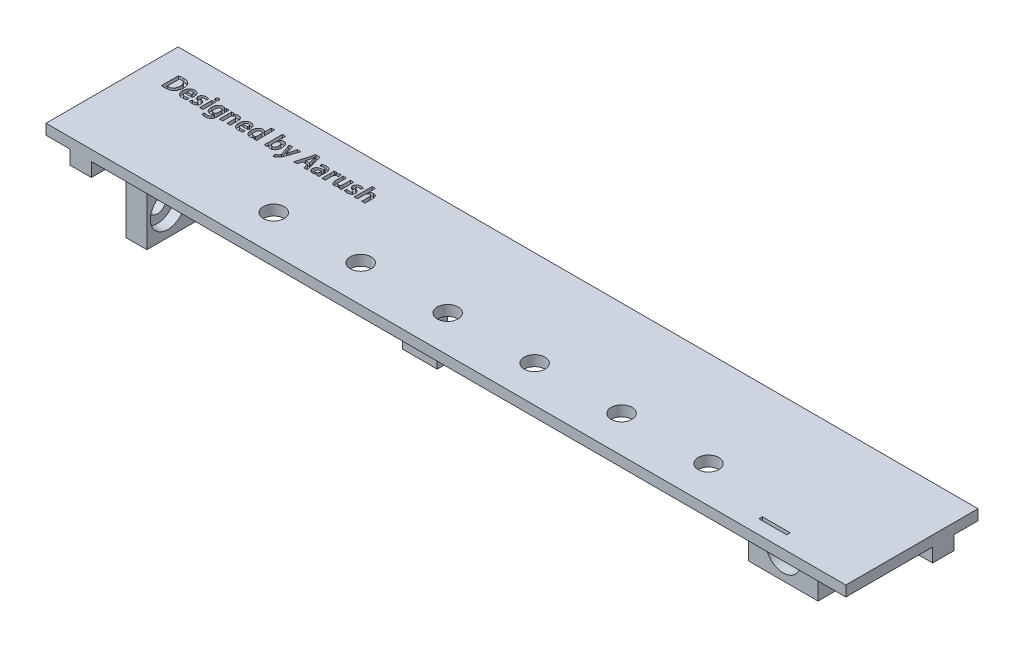
SolidWorks part; units mm, degrees
ref_plane "前视基准面" through (0, 0, 0) normal (0, 0, 1) x (1, 0, 0)
ref_plane "上视基准面" through (0, 0, 0) normal (0, 1, 0) x (1, 0, 0)
ref_plane "右视基准面" through (0, 0, 0) normal (1, 0, 0) x (0, 0, -1)
other "Configuration Table"
sketch "草图18" plane through (0, 0, 0) normal (0, 1, 0) x (1, 0, 0)
  line L1 (0, 0) -> (230, 0)
  line L2 (0, 0) -> (0, 36)
  line L3 (0, 36) -> (230, 36)
  line L4 (230, 0) -> (230, 36)
extrude "凸台-拉伸5" add sketch "草图18" along normal blind 3
sketch "草图20" plane through (0, 3, 0) normal (0, 1, 0) x (1, 0, 0)
  line L0 (0, 36) -> (0, 16)
  line L1 (0, 36) -> (0, 0) construction
  line L2 (0, 16) -> (18.0374, 16)
  line L3 (18.0374, 16) -> (18.0374, 1)
  line L4 (18.0374, 1) -> (0, 1)
  line L5 (0, 1) -> (0, 0)
  line L7 (0, 0) -> (230, 0)
  line L8 (0, 0) -> (0, -2)
  line L9 (0, -2) -> (230, -2)
  line L10 (230, 0) -> (230, -2)
  line M10 (0, 0) -> (230, 0)
extrude "凸台-拉伸6" add sketch "草图20" against normal blind 3 contours L10 L8 L9 M10 region at (115, 3, 1)
sketch "草图21" plane through (0, 3, 0) normal (0, 1, 0) x (1, 0, 0)
  line L0 (20, 16) -> (20, -2)
  line L1 (0, 36) -> (20, 36)
  line L2 (0, 36) -> (0, 16)
  line L3 (0, 16) -> (20, 16)
  line L4 (20, 36) -> (20, 16)
  line L5 (0, -2) -> (230, -2) construction
  line L6 (20, 16) -> (230, 16)
  line L8 (230, -2) -> (230, 36) construction
  line L10 (20, 16) -> (26, 16)
  line L11 (20, 16) -> (20, -2)
  line L12 (20, -2) -> (26, -2)
  line L13 (26, 16) -> (26, -2)
  line M10 (0, -2) -> (230, -2)
extrude "凸台-拉伸7" add sketch "草图21" against normal blind 23 contours L13 L6 L0 M10 region at (23, 3, -7)
sketch "草图23" plane through (0, 0, 0) normal (0, -1, 0) x (1, 0, 0)
  line L2 (230, -36) -> (0, -36) construction
  line L4 (6.95, -17) -> (6.95, -36)
  line L6 (6.95, -36) -> (10, -36)
  line L7 (13.05, -17) -> (13.05, 2)
  line L8 (6.95, -17) -> (6.95, 2)
  line L9 (6.95, 2) -> (13.05, 2)
  line L10 (13.05, -17) -> (13.05, -36)
  line L11 (13.05, -36) -> (10, -36)
extrude "凸台-拉伸8" add sketch "草图23" along normal blind 4 contours L4 L6 L11 L10 L7 L9 L8
sketch "草图24" plane through (0, 0, 0) normal (0, -1, 0) x (1, 0, 0)
  line L3 (20, -26) -> (20, -29.05)
  line L4 (20, -26) -> (20, -22.95)
  line L5 (20, -22.95) -> (230, -22.95)
  line L6 (20, -29.05) -> (230, -29.05)
  line L7 (230, -29.05) -> (230, -22.95)
extrude "凸台-拉伸9" add sketch "草图24" along normal blind 4 contours L3 L6 L7 L5 L4
sketch "草图25" plane through (26, 0, 0) normal (1, 0, 0) x (0, 0, -1)
  line L0 (-2, 0) -> (16, -20)
  circle A0 centre (7, -10) radius 2.6
extrude "切除-拉伸12" cut sketch "草图25" against normal blind 6 contours L0 A0 | L0 A0 region at (26, -9.2618, -7.8202) region at (26, -10.7382, -6.1798)
sketch "草图26" plane through (26, 0, 0) normal (1, 0, 0) x (0, 0, -1)
  circle A0 centre (7, -10) radius 5
extrude "切除-拉伸13" cut sketch "草图26" against normal blind 3
sketch "草图29" plane through (0, 0, 0) normal (0, -1, 0) x (1, 0, 0)
  line L12 (209, -2) -> (201, -2)
  line L13 (209, -2) -> (209, -3)
  line L14 (209, -3) -> (201, -3)
  line L15 (201, -2) -> (201, -3)
  circle A0 centre (55, -8.5) radius 3
  circle A7 centre (80, -8.5) radius 3
  circle A8 centre (105, -8.5) radius 3
  circle A9 centre (130, -8.5) radius 3
  circle A10 centre (155, -8.5) radius 3
  circle A11 centre (180, -8.5) radius 3
  circle A13 centre (205, -8.5) radius 3 [skipped]
  dimension "D1" = 7
extrude "切除-拉伸14" cut sketch "草图29" against normal blind 17
sketch "草图30" plane through (0, 0, 0) normal (0, -1, 0) x (1, 0, 0)
  line L8 (230, 2) -> (230, -22.95) construction
  line L9 (230, -16) -> (190, -16)
  line L11 (190, -16) -> (210, -16)
  line L12 (190, -16) -> (190, -13)
  line L13 (190, -13) -> (210, -13)
  line L14 (210, -16) -> (210, -13)
extrude "凸台-拉伸11" add sketch "草图30" along normal blind 20 contours L9 L14 L13 L12 region at (200, 0, -14.5)
sketch "草图31" plane through (0, 0, -13) normal (0, 0, 1) x (1, 0, 0)
  line L0 (190, 0) -> (210, -20)
  circle A0 centre (200, -10) radius 2.6
extrude "切除-拉伸15" cut sketch "草图31" against normal blind 20 contours L0 A0 | L0 A0 region at (200.7803, -9.2197, -13) region at (199.2197, -10.7803, -13)
sketch "草图32" plane through (0, 0, -13) normal (0, 0, 1) x (1, 0, 0)
  line L0 (210, -20) -> (210, 0) construction
  line L1 (190, -20) -> (210, -20)
  line L2 (190, -20) -> (190, -17)
  line L3 (190, -17) -> (210, -17)
  line L4 (210, -20) -> (210, -17)
extrude "切除-拉伸16" cut sketch "草图32" against normal blind 20
sketch "草图34" plane through (0, 0, -13) normal (0, 0, 1) x (1, 0, 0)
  line L1 (190, 0) -> (210, 0)
  line L2 (190, 0) -> (190, -17)
  line L3 (190, -17) -> (210, -17)
  line L4 (210, 0) -> (210, -17)
  circle A0 centre (200, -10) radius 5
extrude "凸台-拉伸12" add sketch "草图34" along normal blind 3 contours L2 L1 L4 L3 | A0
sketch "草图35" plane through (26, 0, 0) normal (1, 0, 0) x (0, 0, -1)
  line L0 (-2, 0) -> (16, 0) construction
  line L1 (-2, -20) -> (16, -20)
  line L2 (-2, -20) -> (-2, -17)
  line L3 (-2, -17) -> (16, -17)
  line L4 (16, -20) -> (16, -17)
  line L5 (-2, -17) -> (1, -17)
  line L6 (-2, -17) -> (-2, 0)
  line L7 (-2, 0) -> (1, 0)
  line L8 (1, -17) -> (1, 0)
  line M6 (16, 0) -> (-2, 0)
  line M7 (-2, 0) -> (-2, -20)
  line M8 (-2, -20) -> (16, -20)
  line M9 (16, -20) -> (16, 0)
extrude "切除-拉伸17" cut sketch "草图35" against normal blind 6 contours L3 L8 M6 M7 | L3 M7 M8 M9 region at (26, -18.5, -7) region at (26, -8.5, 0.5)
sketch "草图36" plane through (0, 0, 0) normal (0, -1, 0) x (1, 0, 0)
  line L0 (80, -8.5) -> (105, -8.5)
  line L1 (92.5, -16) -> (97.5, -16)
  line L2 (92.5, -16) -> (92.5, -8.5)
  line L3 (92.5, -16) -> (87.5, -16)
  line L5 (87.5, -16) -> (97.5, -16)
  line L6 (87.5, -16) -> (87.5, -13)
  line L7 (87.5, -13) -> (97.5, -13)
  line L8 (97.5, -16) -> (97.5, -13)
extrude "凸台-拉伸13" add sketch "草图36" along normal blind 17 contours L1 L8 L7 L2 | L7 L6 L3 L2 region at (95, 0, -14.5) region at (90, 0, -14.5)
sketch "草图37" plane through (0, 0, -13) normal (0, 0, 1) x (1, 0, 0)
  line L0 (92.5, 0) -> (92.5, -10)
  line L1 (87.5, 0) -> (97.5, 0) construction
  circle A0 centre (92.5, -10) radius 2.6
extrude "切除-拉伸18" cut sketch "草图37" against normal blind 17 contours A0 region at (90.7135, -11.7865, -13)
sketch "草图39" plane through (0, 3, 0) normal (0, 1, 0) x (1, 0, 0)
  text T0 "Designed by Aarush" font "@Adobe Gothic Std B" height in points 16
extrude "切除-拉伸19" cut sketch "草图39" against normal blind 1
